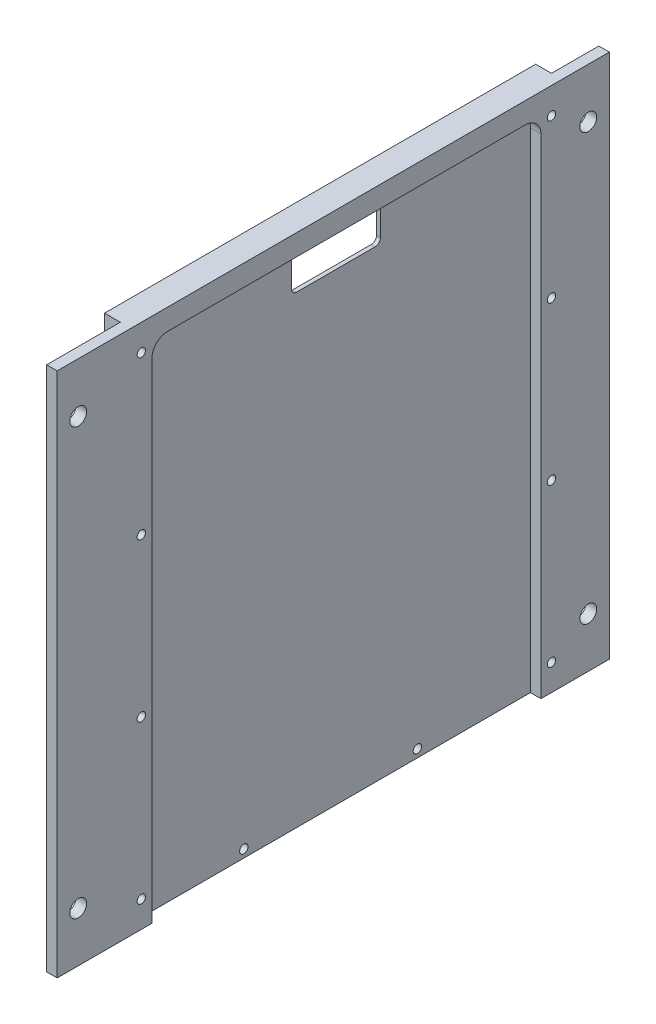
SolidWorks part; units mm, degrees
material "6061-T6 (SS)"
ref_plane "Front Plane" through (0, 0, 0) normal (0, 0, 1) x (1, 0, 0)
ref_plane "Top Plane" through (0, 0, 0) normal (0, 1, 0) x (1, 0, 0)
ref_plane "Right Plane" through (0, 0, 0) normal (1, 0, 0) x (0, 0, -1)
ref_plane "Plane1" through (4.25, 0, 0) normal (1, 0, 0) x (0, 0, -1)
sketch "Sketch1" plane through (4.25, 0, 0) normal (1, 0, 0) x (0, 0, -1)
  line L0 (-4.25, 0) -> (4.25, 0)
  line L1 (4.25, 0) -> (4.25, 227)
  line L2 (4.25, 227) -> (-4.25, 227)
  line L3 (-4.25, 227) -> (-4.25, 0)
  dimension "D1" = 227
  dimension "D2" = 8.5
  dimension "D3" = 4.25
  dimension "D4" = 227
extrude "Boss-Extrude1" add sketch "Sketch1" against normal blind 8.5
ref_plane "Plane2" through (-4.25, 0, 0) normal (-1, 0, 0) x (0, -1, 0)
sketch "Sketch2" plane through (-4.25, 0, 0) normal (-1, 0, 0) x (0, -1, 0)
  line L0 (-6.5, -87.25) -> (-6.5, -4.25)
  line L1 (-6.5, -4.25) -> (-220.5, -4.25)
  line L2 (-220.5, -4.25) -> (-220.5, -87.25)
  line L3 (-220.5, -87.25) -> (-227, -87.25)
  line L4 (-227, -87.25) -> (-227, -95.75)
  line L5 (-227, -95.75) -> (0, -95.75)
  line L6 (0, -95.75) -> (0, -87.25)
  line L7 (0, -87.25) -> (-6.5, -87.25)
  line L8 (0, -4.25) -> (-227, -4.25) construction
  dimension "D1" = 91.5
  dimension "D2" = 6.5
  dimension "D3" = 83
  dimension "D4" = 8.5
  dimension "D5" = 214
extrude "Boss-Extrude2" add sketch "Sketch2" against normal blind 2
sketch "Sketch3" plane through (-2.25, 0, 0) normal (1, 0, 0) x (0, 0, -1)
  line L0 (87.25, 0) -> (87.25, 227)
  line L1 (87.25, 227) -> (95.75, 227)
  line L2 (95.75, 227) -> (95.75, 0)
  line L3 (95.75, 0) -> (87.25, 0)
extrude "Boss-Extrude3" add sketch "Sketch3" along normal blind 6.5
ref_plane "Z_midplane" through (0, 113.5, 0) normal (0, 1, 0) x (1, 0, 0)
sketch "Sketch4" plane through (-4.25, 0, 0) normal (-1, 0, 0) x (0, 0, 1)
  line L0 (-4.75, 6.5) -> (-86.75, 6.5)
  line L1 (-86.75, 6.5) -> (-86.75, 220.5)
  line L2 (-86.75, 220.5) -> (-4.75, 220.5)
  line L3 (-4.75, 220.5) -> (-4.75, 6.5)
extrude "Boss-Extrude4" add sketch "Sketch4" along normal blind 3
sketch "Sketch5" plane through (-2.25, 0, 0) normal (1, 0, 0) x (0, 0, -1)
  line L0 (8.75, 10.5) -> (82.75, 10.5)
  line L1 (82.75, 10.5) -> (82.75, 216.5)
  line L2 (82.75, 216.5) -> (8.75, 216.5)
  line L3 (8.75, 216.5) -> (8.75, 10.5)
  line L4 (87.25, 6.5) -> (4.25, 6.5) construction
  line L5 (4.75, 6.5) -> (4.75, 220.5) construction
  line L6 (86.75, 220.5) -> (86.75, 6.5) construction
  line L7 (4.75, 220.5) -> (86.75, 220.5) construction
  dimension "D1" = 4
  dimension "D2" = 4
  dimension "D3" = 4
  dimension "D4" = 4
extrude "Cut-Extrude1" cut sketch "Sketch5" against normal through all
hole_wizard "M2x0.4 Tapped Hole1" positions "Sketch27" profile "Sketch26" tap size "M2x0.4" standard "ANSI Metric" end condition through all
sketch "Sketch27" plane through (-7.25, 0, 0) normal (-1, 0, 0) x (0, 0, 1)
  line L0 (-86.75, 6.5) -> (-4.75, 6.5) construction
  line L2 (-45.75, 10.5) -> (-45.75, 216.5) construction
  line L3 (-8.75, 10.5) -> (-82.75, 10.5) construction
  line L4 (-82.75, 216.5) -> (-8.75, 216.5) construction
  line L6 (-8.75, 113.5) -> (-82.75, 113.5) construction
  line L7 (-8.75, 216.5) -> (-8.75, 10.5) construction
  line L8 (-82.75, 10.5) -> (-82.75, 216.5) construction
  line L9 (-8.75, 11.5) -> (-4.75, 11.5) construction
  line L10 (-4.75, 6.5) -> (-4.75, 220.5) construction
  point P0 (-6.75, 11.5)
  point P31 (-6.75, 41.5)
  point P32 (-6.75, 71.5)
  point P33 (-6.75, 101.5)
  point P54 (-84.75, 11.5)
  point P55 (-84.75, 41.5)
  point P56 (-84.75, 71.5)
  point P57 (-84.75, 101.5)
  point P60 (-84.75, 125.5)
  point P61 (-84.75, 155.5)
  point P62 (-84.75, 185.5)
  point P63 (-84.75, 215.5)
  point P65 (-6.75, 125.5)
  point P66 (-6.75, 155.5)
  point P67 (-6.75, 185.5)
  point P68 (-6.75, 215.5)
  point P81 (-6.75, 11.5)
  dimension "D1" = 5
  dimension "D4" = 30
  dimension "D3" = 4
sketch "Sketch26" plane through (-7.25, 11.5, -6.75) normal (0, 1, 0) x (0, 0, 1)
  line L0 (0, 0) -> (0, 11.5)
  line L1 (0, 11.5) -> (0.8, 11.5)
  line L2 (0.8, 11.5) -> (0.8, 0)
  line L5 (0.8, 0) -> (0, 0)
  line L11 (0, -6.35) -> (0, 107.95) construction
  dimension "Thru Tap Drill Dia." = 1.6
  dimension "Thru Tap Drill Depth" = 11.5
cosmetic thread "Hole Thread1" parameters "D2"=2
cosmetic thread "Hole Thread2" parameters "D2"=2
cosmetic thread "Hole Thread3" parameters "D2"=2
cosmetic thread "Hole Thread4" parameters "D2"=2
cosmetic thread "Hole Thread5" parameters "D2"=2
cosmetic thread "Hole Thread6" parameters "D2"=2
cosmetic thread "Hole Thread7" parameters "D2"=2
cosmetic thread "Hole Thread8" parameters "D2"=2
cosmetic thread "Hole Thread9" parameters "D2"=2
cosmetic thread "Hole Thread10" parameters "D2"=2
cosmetic thread "Hole Thread11" parameters "D2"=2
cosmetic thread "Hole Thread12" parameters "D2"=2
cosmetic thread "Hole Thread13" parameters "D2"=2
cosmetic thread "Hole Thread14" parameters "D2"=2
cosmetic thread "Hole Thread15" parameters "D2"=2
cosmetic thread "Hole Thread16" parameters "D2"=2
fillet "Fillet2" radius 3 4 edges at (-4.75, 10.5, -8.75) (-4.75, 216.5, -82.75) (-4.75, 216.5, -8.75) (-4.75, 10.5, -82.75) tangent propagation no
fillet "Fillet12" radius 2 1 edges type face fillet first side face at (-6.5, 140.25, -86.75) second side face at (-4.75, 6.5, -45.8125)
ref_plane "Y_midplane" through (0, 0, -45.75) normal (0, 0, 1) x (1, 0, 0)
sketch "Sketch43" plane through (-7.25, 0, 0) normal (-1, 0, 0) x (0, 0, 1)
  line L0 (-45.75, 10.5) -> (-45.75, 216.5) construction
  line L1 (-27.75, 10.5) -> (-30.75, 10.5)
  line L2 (-27.75, 10.5) -> (-27.75, 216.5)
  line L3 (-27.75, 216.5) -> (-30.75, 216.5)
  line L4 (-30.75, 10.5) -> (-30.75, 216.5)
  line L5 (-11.75, 10.5) -> (-79.75, 10.5) construction
  line L6 (-79.75, 216.5) -> (-11.75, 216.5) construction
  line L7 (-63.75, 10.5) -> (-60.75, 10.5)
  line L8 (-63.75, 10.5) -> (-63.75, 216.5)
  line L9 (-63.75, 216.5) -> (-60.75, 216.5)
  line L10 (-60.75, 10.5) -> (-60.75, 216.5)
  dimension "D1" = 3
  dimension "D2" = 30
extrude "Boss-Extrude6" add sketch "Sketch43" against normal blind 3
sketch "Sketch44" plane through (-7.25, 0, 0) normal (-1, 0, 0) x (0, 0, 1)
  line L0 (-8.75, 213.5) -> (-8.75, 13.5) construction
  line L1 (-8.75, 35.8) -> (-82.75, 35.8)
  line L2 (-8.75, 35.8) -> (-8.75, 38.8)
  line L3 (-8.75, 38.8) -> (-82.75, 38.8)
  line L4 (-82.75, 35.8) -> (-82.75, 38.8)
  line L5 (-8.75, 75.8) -> (-82.75, 75.8)
  line L6 (-8.75, 75.8) -> (-8.75, 78.8)
  line L7 (-8.75, 78.8) -> (-82.75, 78.8)
  line L8 (-82.75, 75.8) -> (-82.75, 78.8)
  line L9 (-8.75, 103.5) -> (-82.75, 103.5)
  line L10 (-8.75, 103.5) -> (-8.75, 106.5)
  line L11 (-8.75, 106.5) -> (-82.75, 106.5)
  line L12 (-82.75, 103.5) -> (-82.75, 106.5)
  line L13 (-82.75, 13.5) -> (-82.75, 213.5) construction
  line L14 (-84.75, 6.5) -> (-4.75, 6.5) construction
  line L15 (-8.75, 113.5) -> (-82.75, 113.5) construction
  line L16 (-8.75, 191.2) -> (-8.75, 188.2)
  line L17 (-8.75, 191.2) -> (-82.75, 191.2)
  line L18 (-82.75, 191.2) -> (-82.75, 188.2)
  line L19 (-8.75, 188.2) -> (-82.75, 188.2)
  line L20 (-8.75, 151.2) -> (-8.75, 148.2)
  line L21 (-8.75, 151.2) -> (-82.75, 151.2)
  line L22 (-82.75, 151.2) -> (-82.75, 148.2)
  line L23 (-8.75, 148.2) -> (-82.75, 148.2)
  line L24 (-8.75, 123.5) -> (-8.75, 120.5)
  line L25 (-8.75, 123.5) -> (-82.75, 123.5)
  line L26 (-82.75, 123.5) -> (-82.75, 120.5)
  line L27 (-8.75, 120.5) -> (-82.75, 120.5)
  dimension "D1" = 3
  dimension "D2" = 29.3
  dimension "D3" = 40
  dimension "D4" = 100
extrude "Boss-Extrude7" add sketch "Sketch44" against normal up to surface (3 mm away) up to face at (-4.25, 113.5, -29.25)
fillet "Fillet4" radius 3 80 edges at (-5.75, 188.2, -8.75) (-5.75, 216.5, -60.75) (-5.75, 35.8, -82.75) (-5.75, 38.8, -82.75) (-5.75, 75.8, -82.75) (-5.75, 78.8, -82.75) (-5.75, 103.5, -82.75) (-5.75, 106.5, -82.75) (-5.75, 120.5, -82.75) (-5.75, 123.5, -82.75) (-5.75, 10.5, -60.75) (-5.75, 10.5, -63.75) (-5.75, 10.5, -27.75) (-5.75, 10.5, -30.75) (-5.75, 35.8, -8.75) (-5.75, 38.8, -8.75) (-5.75, 75.8, -8.75) (-5.75, 78.8, -8.75) (-5.75, 103.5, -8.75) (-5.75, 106.5, -8.75) (-5.75, 123.5, -8.75) (-5.75, 120.5, -8.75) (-5.75, 151.2, -8.75) (-5.75, 148.2, -8.75) (-5.75, 216.5, -27.75) (-5.75, 216.5, -63.75) (-5.75, 216.5, -30.75) (-5.75, 191.2, -8.75) (-5.75, 148.2, -82.75) (-5.75, 151.2, -82.75) (-5.75, 188.2, -82.75) (-5.75, 191.2, -82.75) (-5.75, 191.2, -60.75) (-5.75, 188.2, -60.75) (-5.75, 191.2, -63.75) (-5.75, 188.2, -63.75) (-5.75, 191.2, -27.75) (-5.75, 191.2, -30.75) (-5.75, 188.2, -27.75) (-5.75, 188.2, -30.75) (-5.75, 151.2, -27.75) (-5.75, 151.2, -30.75) (-5.75, 148.2, -27.75) (-5.75, 148.2, -30.75) (-5.75, 151.2, -60.75) (-5.75, 148.2, -60.75) (-5.75, 151.2, -63.75) (-5.75, 148.2, -63.75) (-5.75, 123.5, -27.75) (-5.75, 123.5, -30.75) (-5.75, 120.5, -27.75) (-5.75, 120.5, -30.75) (-5.75, 103.5, -27.75) (-5.75, 103.5, -30.75) (-5.75, 106.5, -27.75) (-5.75, 106.5, -30.75) (-5.75, 123.5, -60.75) (-5.75, 120.5, -60.75) (-5.75, 123.5, -63.75) (-5.75, 120.5, -63.75) (-5.75, 103.5, -60.75) (-5.75, 106.5, -60.75) (-5.75, 103.5, -63.75) (-5.75, 106.5, -63.75) (-5.75, 78.8, -30.75) (-5.75, 75.8, -27.75) (-5.75, 75.8, -30.75) (-5.75, 78.8, -27.75) (-5.75, 75.8, -60.75) (-5.75, 78.8, -60.75) (-5.75, 75.8, -63.75) (-5.75, 78.8, -63.75) (-5.75, 35.8, -27.75) (-5.75, 35.8, -30.75) (-5.75, 38.8, -27.75) (-5.75, 38.8, -30.75) (-5.75, 35.8, -63.75) (-5.75, 35.8, -60.75) (-5.75, 38.8, -63.75) (-5.75, 38.8, -60.75) tangent propagation no
sketch "Sketch50" plane through (-4.25, 0, 0) normal (1, 0, 0) x (0, 0, -1)
  line L0 (79.75, 216.5) -> (11.75, 216.5) construction
  line L1 (8.75, 213.5) -> (8.75, 13.5) construction
  line L2 (11.75, 10.5) -> (79.75, 10.5) construction
  line L3 (82.75, 13.5) -> (82.75, 213.5) construction
  line L4 (79.75, 216.5) -> (11.75, 216.5)
  line L5 (8.75, 213.5) -> (8.75, 13.5)
  line L6 (11.75, 10.5) -> (79.75, 10.5)
  line L7 (82.75, 13.5) -> (82.75, 213.5)
  arc A0 (82.75, 213.5) -> (79.75, 216.5) centre (79.75, 213.5) ccw construction
  arc A1 (11.75, 216.5) -> (8.75, 213.5) centre (11.75, 213.5) ccw construction
  arc A2 (8.75, 13.5) -> (11.75, 10.5) centre (11.75, 13.5) ccw construction
  arc A3 (79.75, 10.5) -> (82.75, 13.5) centre (79.75, 13.5) ccw construction
  arc A4 (82.75, 213.5) -> (79.75, 216.5) centre (79.75, 213.5) ccw
  arc A5 (11.75, 216.5) -> (8.75, 213.5) centre (11.75, 213.5) ccw
  arc A6 (8.75, 13.5) -> (11.75, 10.5) centre (11.75, 13.5) ccw
  arc A7 (79.75, 10.5) -> (82.75, 13.5) centre (79.75, 13.5) ccw
extrude "webExtrude" add sketch "Sketch50" against normal blind 0.75
sketch "Sketch51" plane through (-5, 0, 0) normal (-1, 0, 0) x (0, 0, 1)
  line L0 (-57.75, 216.5) -> (-33.75, 216.5) construction
  line L1 (-54.225, 216.5) -> (-37.275, 216.5)
  line L2 (-54.225, 216.5) -> (-54.225, 208.7)
  line L3 (-54.225, 208.7) -> (-37.275, 208.7)
  line L4 (-37.275, 216.5) -> (-37.275, 208.7)
  point P4 (-45.75, 216.5)
  dimension "D1" = 7.8
  dimension "D2" = 16.95
extrude "12pinCutout" cut sketch "Sketch51" against normal through all both and the other way through all
mirror "Mirror10" about plane through (0, 113.5, 0) normal (0, 1, 0) of "12pinCutout"
fillet "Fillet18" radius 1 8 edges at (-4.625, 216.5, -37.275) (-4.625, 216.5, -54.225) (-4.625, 208.7, -54.225) (-4.625, 208.7, -37.275) (-4.625, 10.5, -37.275) (-4.625, 18.3, -37.275) (-4.625, 18.3, -54.225) (-4.625, 10.5, -54.225)
hole_wizard "M2x0.4 Tapped Hole2" positions "Sketch45" profile "Sketch46" tap size "M2x0.4" standard "ANSI Metric" end condition through all
sketch "Sketch45" plane through (-7.25, 0, 0) normal (-1, 0, 0) x (0, 0, 1)
  line L0 (-44.75, 6.5) -> (-44.75, 220.5) construction
  line L1 (-84.75, 6.5) -> (-4.75, 6.5) construction
  line L20 (-4.75, 113.5) -> (-86.75, 113.5) construction
  line L21 (-4.75, 6.5) -> (-4.75, 220.5) construction
  line L23 (-62.25, 75.8) -> (-62.25, 78.8) construction
  line L24 (-79.75, 75.8) -> (-66.75, 75.8) construction
  line L25 (-66.75, 78.8) -> (-79.75, 78.8) construction
  line L27 (-60.75, 77.3) -> (-63.75, 77.3) construction
  line L28 (-60.75, 41.8) -> (-60.75, 72.8) construction
  line L29 (-63.75, 72.8) -> (-63.75, 41.8) construction
  line L30 (-79.75, 216.5) -> (-11.75, 216.5) construction
  line L31 (-87.25, 227) -> (-87.25, 0) construction
  point P2 (-61.25, 105)
  point P36 (-44.75, 6.5)
  point P68 (-28.25, 105)
  point P70 (-61.25, 122)
  point P71 (-28.25, 122)
  point P73 (-62.25, 77.3)
  point P92 (-27.25, 77.3)
  dimension "D1" = 4
  dimension "D2" = 0.5
  dimension "D3" = 16.5
  dimension "D4" = 17
sketch "Sketch46" plane through (-7.25, 105, -61.25) normal (0, 1, 0) x (0, 0, 1)
  line L0 (0, 0) -> (0, 11.5)
  line L1 (0, 11.5) -> (0.8, 11.5)
  line L2 (0.8, 11.5) -> (0.8, 0)
  line L5 (0.8, 0) -> (0, 0)
  line L11 (0, -6.35) -> (0, 107.95) construction
  dimension "Thru Tap Drill Dia." = 1.6
  dimension "Thru Tap Drill Depth" = 11.5
cosmetic thread "Hole Thread17" parameters "D2"=2
cosmetic thread "Hole Thread20" parameters "D2"=2
cosmetic thread "Hole Thread21" parameters "D2"=2
cosmetic thread "Hole Thread23" parameters "D2"=2
cosmetic thread "Hole Thread41" parameters "D2"=2
cosmetic thread "Hole Thread42" parameters "D2"=2
ref_plane "chamferStart" through (0, 212.5, 0) normal (0, 1, 0) x (1, 0, 0)
sketch "Sketch36" plane through (4.25, 0, 0) normal (1, 0, 0) x (0, 0, -1)
  line L1 (4.25, 207.45) -> (-1.25, 207.45)
  line L2 (4.25, 207.45) -> (4.25, 201.95)
  line L3 (4.25, 201.95) -> (-1.25, 201.95)
  line L4 (-1.25, 207.45) -> (-1.25, 201.95)
  line L5 (-4.25, 227) -> (-4.25, 0) construction
  line L6 (4.25, 207.45) -> (-1.25, 201.95) construction
  line L7 (4.25, 220.5) -> (87.25, 220.5) construction
  dimension "D1" = 13.05
  dimension "D2" = 5.5
  dimension "D3" = 5.5
  dimension "D4" = 8.5
extrude "Boss-Extrude5" add sketch "Sketch36" against normal up to surface (6.5 mm away) up to face at (-2.25, 12.3, -6.75)
ref_plane "Plane13" through (0, 113.5, 0) normal (0, 1, 0) x (1, 0, 0)
ref_plane "center_Y" through (0, 0, -45.75) normal (0, 0, 1) x (1, 0, 0)
ref_plane "center_Z" through (0, 113.5, 0) normal (0, 1, 0) x (1, 0, 0)
sketch "Sketch58" plane through (-2.25, 0, 0) normal (1, 0, 0) x (0, 0, -1)
  line L0 (11.75, 10.5) -> (79.75, 10.5) construction
  line L1 (43.25, 10.5) -> (48.25, 10.5)
  line L2 (43.25, 10.5) -> (43.25, 12)
  line L3 (43.25, 12) -> (48.25, 12)
  line L4 (48.25, 10.5) -> (48.25, 12)
  line L5 (87.25, 6.5) -> (4.25, 6.5) construction
  point P6 (45.75, 6.5)
  point P11 (45.75, 10.5)
  dimension "D1" = 5
  dimension "D2" = 5.5
extrude "Boss-Extrude9" add sketch "Sketch58" against normal up to surface (2.75 mm away) up to face at (-5, 18.775, -45.75)
sketch "Sketch63" plane through (0, 0, 0) normal (0, -1, 0) x (-1, 0, 0)
  line L1 (-4.25, 95.75) -> (7.9173, 95.75)
  line L2 (-4.25, 95.75) -> (-4.25, -4.25)
  line L3 (-4.25, -4.25) -> (7.9173, -4.25)
  line L4 (7.9173, 95.75) -> (7.9173, -4.25)
  dimension "D1" = 12.1673
  dimension "D2" = 100
extrude "Cut-Extrude28" cut sketch "Sketch63" against normal up to surface (120.5 mm away) up to face at (-6.125, 120.5, -45.75)
sketch "Sketch64" plane through (0, 227, 0) normal (0, 1, 0) x (1, 0, 0)
  line L1 (4.25, -4.25) -> (-12.9489, -4.25)
  line L2 (4.25, -4.25) -> (4.25, 100.8651)
  line L3 (4.25, 100.8651) -> (-12.9489, 100.8651)
  line L4 (-12.9489, -4.25) -> (-12.9489, 100.8651)
  dimension "D1" = 17.1989
  dimension "D2" = 105.1151
extrude "Cut-Extrude29" cut sketch "Sketch64" against normal up to surface (6.5 mm away) up to face at (-4.75, 220.5, -45.6875)
sketch "Sketch65" plane through (0, 220.5, 0) normal (0, 1, 0) x (1, 0, 0)
  line L1 (4.25, 95.75) -> (-2.25, 95.75)
  line L2 (4.25, 95.75) -> (4.25, 87.25)
  line L3 (4.25, 87.25) -> (-2.25, 87.25)
  line L4 (-2.25, 95.75) -> (-2.25, 87.25)
  line L5 (4.25, -4.25) -> (-2.25, -4.25)
  line L6 (4.25, -4.25) -> (4.25, 4.25)
  line L7 (4.25, 4.25) -> (-2.25, 4.25)
  line L8 (-2.25, -4.25) -> (-2.25, 4.25)
extrude "Cut-Extrude30" cut sketch "Sketch65" against normal through all
sketch "Sketch69" plane through (-2.25, 0, 0) normal (1, 0, 0) x (0, 0, -1)
  line L0 (-4.25, 120.5) -> (8.75, 120.5) construction
  line L1 (-4.25, 220.5) -> (-9.25, 220.5)
  line L2 (-4.25, 220.5) -> (-4.25, 120.5)
  line L3 (-4.25, 120.5) -> (-9.25, 120.5)
  line L4 (-9.25, 220.5) -> (-9.25, 120.5)
  dimension "D1" = 5
  dimension "D2" = 0
extrude "Boss-Extrude10" add sketch "Sketch69" against normal up to surface (2 mm away) up to face at (-4.25, 158, 0.875)
sketch "Sketch70" plane through (-2.25, 0, 0) normal (1, 0, 0) x (0, 0, -1)
  line L0 (-9.25, 120.5) -> (8.75, 120.5) construction
  line L1 (8.75, 213.5) -> (8.75, 120.5) construction
  line L3 (95.75, 120.5) -> (95.75, 220.5) construction
  point P0 (-5.25, 211)
  point P1 (-5.25, 130)
  point P2 (91.75, 130)
  point P3 (91.75, 211)
  point P8 (-14.25, 127.6301)
  point P11 (0, 0)
  point P13 (87.75, 209.5)
  dimension "D1" = 97
  dimension "D2" = 97
  dimension "D3" = 81
  dimension "D4" = 9.5
  dimension "D5" = 4
  dimension "D6" = 4
  dimension "D7" = 14
  dimension "D8" = 81
hole_wizard "M3 Clearance Hole2" positions "Sketch71" profile "Sketch72" hole size "M3" standard "ISO" end condition through all
sketch "Sketch71" plane through (-2.25, 0, 0) normal (1, 0, 0) x (0, 0, -1)
  point P0 (-5.25, 130)
  point P3 (-5.25, 211)
  point P6 (91.75, 211)
  point P9 (91.75, 130)
sketch "Sketch72" plane through (-2.25, 130, 5.25) normal (0, 1, 0) x (0, 0, -1)
  line L0 (0, 0) -> (0, 5)
  line L1 (0, 5) -> (1.6, 5)
  line L2 (1.6, 5) -> (1.6, 0)
  line L5 (1.6, 0) -> (0, 0)
  line L11 (0, -6.35) -> (0, 107.95) construction
  dimension "Thru Hole Dia." = 3.2
  dimension "Thru Hole Depth" = 5
equation "\"D2@Sketch56\"=\"D1@Sketch56\""
equation "\"D3@Sketch48\"=\"D2@Sketch48\""
